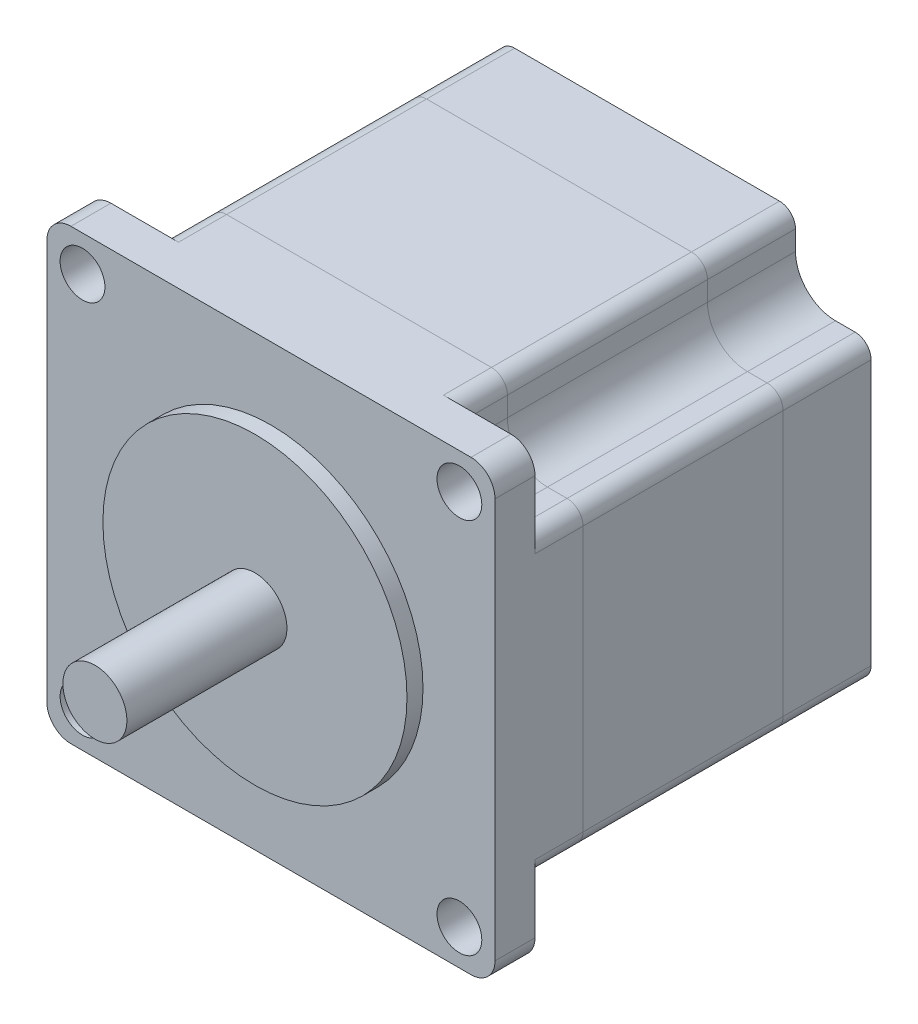
SolidWorks part; units mm, degrees
ref_plane "Front Plane" through (0, 0, 0) normal (0, 0, 1) x (1, 0, 0)
ref_plane "Top Plane" through (0, 0, 0) normal (0, 1, 0) x (1, 0, 0)
ref_plane "Right Plane" through (0, 0, 0) normal (1, 0, 0) x (0, 0, -1)
ref_plane "Plane1" through (0, 0, 0) normal (0, 0, -1) x (-1, 0, 0)
ref_axis "Axis Motor" through (0, 0, -24.3683) along (0, 0, 1)
sketch "Sketch1" plane through (0, 0, 0) normal (0, 0, -1) x (-1, 0, 0)
  line L0 (-23, 28) -> (-28, 23)
  line L1 (-28, 23) -> (-28, -23)
  line L2 (-28, -23) -> (-23, -28)
  line L3 (-23, -28) -> (23, -28)
  line L4 (23, -28) -> (28, -23)
  line L5 (28, -23) -> (28, 23)
  line L6 (28, 23) -> (23, 28)
  line L7 (23, 28) -> (-23, 28)
  line L8 (0, 0) -> (28, 0) construction
  line L9 (0, 0) -> (0, -13.2452) construction
  point P8 (0, -28)
  point P10 (28, 0)
  dimension "D1" = 56
  dimension "D2" = 56
  dimension "D3" = 135
  dimension "D4" = 5
extrude "Boss-Extrude1" add sketch "Sketch1" against normal blind 11.5
sketch "Sketch2" plane through (0, 0, 11.5) normal (0, 0, 1) x (1, 0, 0)
  line L12 (23, 28) -> (-23, 28)
  line L13 (-23, 28) -> (-28, 23)
  line L14 (-28, 23) -> (-28, -23)
  line L15 (-28, -23) -> (-23, -28)
  line L16 (-23, -28) -> (23, -28)
  line L17 (23, -28) -> (28, -23)
  line L18 (28, -23) -> (28, 23)
  line L19 (28, 23) -> (23, 28)
  line L20 (23, 28) -> (-23, 28)
  line L21 (-23, 28) -> (-28, 23)
  line L22 (-28, 23) -> (-28, -23)
  line L23 (-28, -23) -> (-23, -28)
  line L24 (-23, -28) -> (23, -28)
  line L25 (23, -28) -> (28, -23)
  line L26 (28, -23) -> (28, 23)
  line L27 (28, 23) -> (23, 28)
  dimension "D1" = 0
extrude "Boss-Extrude2" add sketch "Sketch2" along normal blind 25.5
sketch "Sketch3" plane through (0, 0, 37) normal (0, 0, 1) x (1, 0, 0)
  line L15 (28, 23) -> (23, 28)
  line L16 (23, 28) -> (-23, 28)
  line L17 (-23, 28) -> (-28, 23)
  line L18 (-28, 23) -> (-28, -23)
  line L19 (-28, -23) -> (-23, -28)
  line L20 (-23, -28) -> (23, -28)
  line L21 (23, -28) -> (28, -23)
  line L22 (28, -23) -> (28, 23)
  line L24 (28, 28) -> (-28, 28)
  line L26 (-28, 28) -> (-28, -28)
  line L28 (-28, -28) -> (28, -28)
  line L30 (28, -28) -> (28, 28)
  dimension "D1" = 0
extrude "Boss-Extrude3" add sketch "Sketch3" along normal blind 10
ref_plane "Plane2" through (0, 0, 3.65) normal (0, 0, 1) x (1, 0, 0)
sketch "Sketch4" plane through (0, 0, 3.65) normal (0, 0, 1) x (1, 0, 0)
  line L0 (-31, 1.25) -> (-31, 0.65)
  line L1 (-31, 0.65) -> (-21, 0.65)
  line L2 (-21, 0.65) -> (-21, 1.25)
  line L3 (-21, 1.25) -> (-31, 1.25)
  line L4 (-31, 0.65) -> (-21, 0.65) construction
revolve "Revolve1" add sketch "Sketch4" angle 360 about L4 reverse direction yes
sketch "Sketch5" plane through (0, 0, 3.65) normal (0, 0, 1) x (1, 0, 0)
  line L0 (-31, -0.05) -> (-31, -0.65)
  line L1 (-31, -0.65) -> (-21, -0.65)
  line L2 (-21, -0.65) -> (-21, -0.05)
  line L3 (-21, -0.05) -> (-31, -0.05)
  line L4 (-31, -0.65) -> (-21, -0.65) construction
revolve "Revolve2" add sketch "Sketch5" angle 360 about L4 reverse direction yes
ref_plane "Plane3" through (0, 0, 4.95) normal (0, 0, 1) x (1, 0, 0)
sketch "Sketch6" plane through (0, 0, 4.95) normal (0, 0, 1) x (1, 0, 0)
  line L0 (-31, -0.05) -> (-31, -0.65)
  line L1 (-31, -0.65) -> (-21, -0.65)
  line L2 (-21, -0.65) -> (-21, -0.05)
  line L3 (-21, -0.05) -> (-31, -0.05)
  line L4 (-31, -0.65) -> (-21, -0.65) construction
revolve "Revolve3" add sketch "Sketch6" angle 360 about L4 reverse direction yes
sketch "Sketch7" plane through (0, 0, 4.95) normal (0, 0, 1) x (1, 0, 0)
  line L0 (-31, 1.25) -> (-31, 0.65)
  line L1 (-31, 0.65) -> (-21, 0.65)
  line L2 (-21, 0.65) -> (-21, 1.25)
  line L3 (-21, 1.25) -> (-31, 1.25)
  line L4 (-31, 0.65) -> (-21, 0.65) construction
revolve "Revolve4" add sketch "Sketch7" angle 360 about L4 reverse direction yes
ref_plane "Plane4" through (0, 0, 0) normal (0, -1, 0) x (1, 0, 0)
sketch "Sketch8" plane through (0, 0, 0) normal (0, -1, 0) x (1, 0, 0)
  line L0 (4, 69) -> (0, 69)
  line L1 (0, 69) -> (0, 47)
  line L2 (0, 47) -> (19, 47)
  line L3 (19, 47) -> (19, 49)
  line L4 (19, 49) -> (4, 49)
  line L5 (4, 49) -> (4, 69)
  line L6 (0, 69) -> (0, 47) construction
  line L7 (28, 47) -> (-28, 47) construction
  line L8 (0, -24.3683) -> (0, 71.8516) construction
  dimension "D1" = 2
  dimension "D2" = 20
  dimension "D3" = 4
  dimension "D4" = 19
revolve "Revolve5" add sketch "Sketch8" angle 360 about L6 reverse direction yes
hole_wizard "Hole1" positions "Sketch10" profile "Sketch9" legacy
sketch "Sketch10" plane through (0, 0, 47) normal (0, 0, 1) x (1, 0, 0)
  line L1 (-23.55, 23.55) -> (0, 0) construction
  line L2 (0, 0) -> (0, 42.4264) construction
  circle A0 centre (0, 0) radius 33.3047 construction
  circle A1 centre (-23.55, 23.55) radius 2.8
  point P0 (-23.55, 23.55)
  dimension "D1" = 41.5
  dimension "D3" = 5.6
  dimension "D2" = 45
sketch "Sketch9" plane through (-23.55, 23.55, 47) normal (1, 0, 0) x (0, -1, 0)
  line L0 (0, 0) -> (0, 5)
  line L1 (0, 5) -> (2.8, 5)
  line L2 (2.8, 5) -> (2.8, 0)
  line L3 (2.8, 0) -> (0, 0)
  line L4 (0, 110) -> (0, -10) construction
  dimension "Diameter" = 5.6
  dimension "Depth" = 5
hole_wizard "Hole2" positions "Sketch12" profile "Sketch11" legacy
sketch "Sketch12" plane through (0, 0, 47) normal (0, 0, 1) x (1, 0, 0)
  line L0 (0, 0) -> (-36.6834, 0) construction
  point P0 (-23.55, -23.55)
  point P5 (-23.55, 23.55)
sketch "Sketch11" plane through (-23.55, -23.55, 47) normal (1, 0, 0) x (0, -1, 0)
  line L0 (0, 0) -> (0, 5)
  line L1 (0, 5) -> (2.8, 5)
  line L2 (2.8, 5) -> (2.8, 0)
  line L3 (2.8, 0) -> (0, 0)
  line L4 (0, 110) -> (0, -10) construction
  dimension "Diameter" = 5.6
  dimension "Depth" = 5
mirror "Mirror2" about plane through (0, 0, 0) normal (1, 0, 0) of "Hole1", "Hole2"
sketch "Sketch34" plane through (0, 0, 37) normal (0, 0, -1) x (-1, 0, 0)
  line L0 (0, 0) -> (0, 60.2383) construction
  line L1 (0, 0) -> (33.4585, 0) construction
  line L2 (18.55, 23.55) -> (18.55, 34.6712)
  line L3 (18.55, 34.6712) -> (31.9747, 34.6712)
  line L4 (31.9747, 34.6712) -> (31.9747, 18.55)
  line L5 (23.55, 18.55) -> (31.9747, 18.55)
  line L6 (23.55, -18.55) -> (31.9747, -18.55)
  line L7 (31.9747, -34.6712) -> (31.9747, -18.55)
  line L8 (18.55, -34.6712) -> (31.9747, -34.6712)
  line L9 (18.55, -23.55) -> (18.55, -34.6712)
  line L10 (-18.55, -23.55) -> (-18.55, -34.6712)
  line L11 (-18.55, -34.6712) -> (-31.9747, -34.6712)
  line L12 (-31.9747, -34.6712) -> (-31.9747, -18.55)
  line L13 (-23.55, -18.55) -> (-31.9747, -18.55)
  line L14 (-23.55, 18.55) -> (-31.9747, 18.55)
  line L15 (-31.9747, 34.6712) -> (-31.9747, 18.55)
  line L16 (-18.55, 34.6712) -> (-31.9747, 34.6712)
  line L17 (-18.55, 23.55) -> (-18.55, 34.6712)
  arc A0 (18.55, 23.55) -> (23.55, 18.55) centre (23.55, 23.55) ccw
  circle A1 centre (23.55, 23.55) radius 2.8 construction
  arc A5 (18.55, -23.55) -> (23.55, -18.55) centre (23.55, -23.55) cw
  arc A6 (-18.55, -23.55) -> (-23.55, -18.55) centre (-23.55, -23.55) ccw
  arc A7 (-18.55, 23.55) -> (-23.55, 18.55) centre (-23.55, 23.55) cw
  dimension "D1" = 10
extrude "Cut-Extrude9" cut sketch "Sketch34" along normal through all and the other way offset from surface 5 other way up to face at (26.35, -23.55, 47)
fillet "Fillet3" radius 2 8 edges at (18.55, -28, 21) (28, -18.55, 21) (-18.55, -28, 21) (-28, -18.55, 21) (-28, 18.55, 21) (-18.55, 28, 21) (28, 18.55, 21) (18.55, 28, 21)
fillet "Fillet4" radius 3 4 edges at (28, 28, 44.5) (-28, 28, 44.5) (28, -28, 44.5) (-28, -28, 44.5)
sketch "Sketch17" plane through (0, 0, 0) normal (0, 0, -1) x (-1, 0, 0)
  circle A0 centre (0, 0) radius 4 construction
  circle A1 centre (0, 0) radius 4
extrude "Boss-Extrude4" add sketch "Sketch17" along normal blind 12
sketch "Sketch31" plane through (28, 0, 0) normal (1, 0, 0) x (0, 0, -1)
  line L0 (0, 16.55) -> (0, -16.55) construction
  line L1 (-11, 32.881) -> (-36, 32.881)
  line L2 (-11, 32.881) -> (-11, -32.0284)
  line L3 (-11, -32.0284) -> (-36, -32.0284)
  line L4 (-36, 32.881) -> (-36, -32.0284)
  line L7 (-47, -25) -> (-47, 25) construction
  dimension "D1" = 11
  dimension "D2" = 11
split line "Split Line2"
